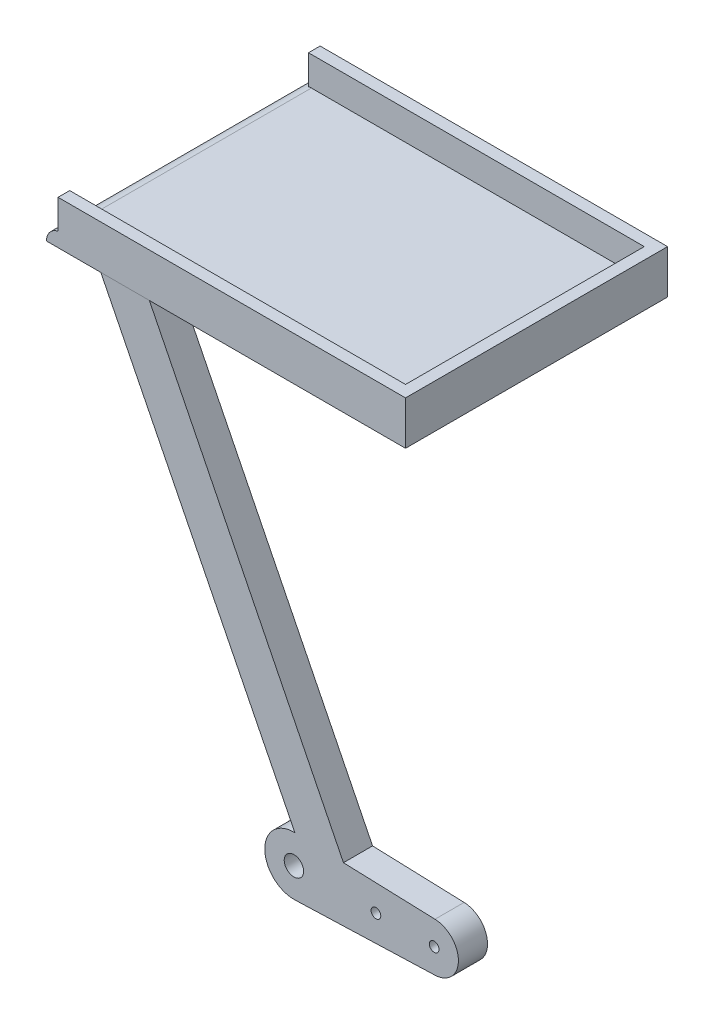
SolidWorks part; units mm, degrees
ref_plane "Front Plane" through (0, 0, 0) normal (0, 0, 1) x (1, 0, 0)
ref_plane "Top Plane" through (0, 0, 0) normal (0, 1, 0) x (1, 0, 0)
ref_plane "Right Plane" through (0, 0, 0) normal (1, 0, 0) x (0, 0, -1)
sketch "Sketch1" plane through (0, 0, 0) normal (0, 0, 1) x (1, 0, 0)
  line L0 (0.1038, 2.9982) -> (14.5365, 2.4985) construction
  line L1 (0.1038, -2.9982) -> (14.5365, -2.4985)
  line L5 (5.1038, 2.8251) -> (0.1038, 2.9982) construction
  line L6 (5.1038, 2.8251) -> (14.5365, 2.4985)
  line L7 (0.1038, 2.9982) -> (-19.8962, 42.9982)
  line L8 (-19.8962, 42.9982) -> (-14.8962, 42.9982)
  line L9 (-14.8962, 42.9982) -> (5.1038, 2.8251)
  circle A0 centre (0, 0) radius 1
  circle A1 centre (8.45, 0) radius 0.5
  circle A2 centre (14.45, 0) radius 0.5
  arc A3 (0.1038, 2.9982) -> (0.1038, -2.9982) centre (0, 0) ccw
  arc A4 (14.5365, 2.4985) -> (14.5365, -2.4985) centre (14.45, 0) cw
  dimension "D1" = 2
  dimension "D2" = 1
  dimension "D5" = 3
  dimension "D6" = 2.5
  dimension "D9" = 20
  dimension "D3" = 8.45
  dimension "D4" = 14.45
  dimension "D7" = 5
  dimension "D8" = 5
  dimension "D10" = 40
extrude "Boss-Extrude1" add sketch "Sketch1" along normal blind 3
sketch "Sketch4" plane through (0, 42.9982, 0) normal (0, 1, 0) x (1, 0, 0)
  line L0 (-14.8962, -3) -> (-19.8962, -3) construction
  line L1 (-25.5, 24) -> (11.5, 24)
  line L2 (-25.5, 24) -> (-25.5, -3)
  line L3 (-25.5, -3) -> (11.5, -3)
  line L4 (11.5, 24) -> (11.5, -3)
  dimension "D1" = 37
  dimension "D2" = 27
  dimension "D3" = 11.5
extrude "Boss-Extrude3" add sketch "Sketch4" along normal blind 1.5 separate body
sketch "Sketch5" plane through (0, 44.4982, 0) normal (0, 1, 0) x (1, 0, 0)
  line L1 (-25.5, 24) -> (11.5, 24) construction
  line L2 (-25.5, 24) -> (-25.5, -3) construction
  line L3 (-25.5, -3) -> (11.5, -3) construction
  line L4 (11.5, 24) -> (11.5, -3) construction
  line L8 (-24.3, 22.8) -> (-24.3, 24)
  line L9 (-24.3, 24) -> (11.5, 24)
  line L10 (11.5, 24) -> (11.5, -3)
  line L11 (11.5, -3) -> (-24.3, -3)
  line L12 (-24.3, -1.8) -> (10.3, -1.8)
  line L13 (10.3, -1.8) -> (10.3, 22.8)
  line L14 (10.3, 22.8) -> (-24.3, 22.8)
  line L15 (-24.3, 22.8) -> (-24.3, -1.8)
  line L16 (-24.3, -1.8) -> (10.3, -1.8)
  line L17 (10.3, -1.8) -> (10.3, 22.8)
  line L18 (10.3, 22.8) -> (-24.3, 22.8)
  line L20 (-24.3, -3) -> (-24.3, -1.8)
  dimension "D1" = 1.2
extrude "Boss-Extrude4" add sketch "Sketch5" along normal blind 3
fillet "Fillet1" radius 1.5 1 edges at (-25.5, 44.4982, -10.5)
